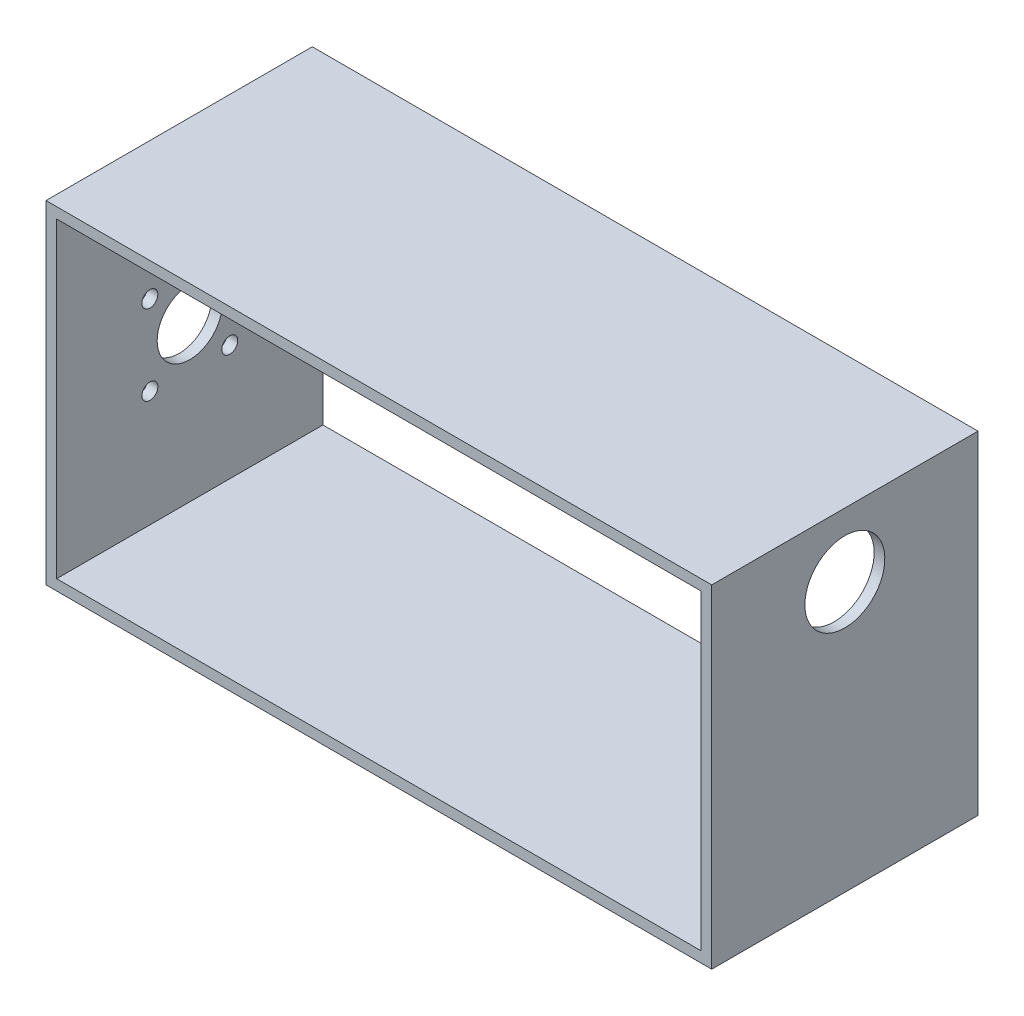
SolidWorks part; units mm, degrees
ref_plane "Ebene vorne" through (0, 0, 0) normal (0, 0, 1) x (1, 0, 0)
ref_plane "Ebene oben" through (0, 0, 0) normal (0, 1, 0) x (1, 0, 0)
ref_plane "Ebene rechts" through (0, 0, 0) normal (1, 0, 0) x (0, 0, -1)
sketch "Skizze1" plane through (0, 0, 0) normal (0, 0, 1) x (1, 0, 0)
  line L1 (0, 125) -> (250, 125)
  line L2 (0, 125) -> (0, 0)
  line L3 (0, 0) -> (250, 0)
  line L4 (250, 125) -> (250, 0)
  line L5 (246, 121) -> (4, 121)
  line L6 (246, 121) -> (246, 4)
  line L7 (246, 4) -> (4, 4)
  line L8 (4, 121) -> (4, 4)
  dimension "D1" = 250
  dimension "D2" = 125
  dimension "D3" = 4
  dimension "D4" = 4
  dimension "D5" = 4
  dimension "D6" = 4
extrude "Aufsatz-Linear austragen1" add sketch "Skizze1" along normal blind 100
sketch "Skizze2" plane through (0, 0, 0) normal (-1, 0, 0) x (0, 0, 1)
  line L0 (0, 125) -> (100, 0) construction
  circle A0 centre (50, 62.5) radius 12.25
extrude "Schnitt-Linear austragen1" cut sketch "Skizze2" against normal blind 10
sketch "Skizze3" plane through (246, 0, 0) normal (-1, 0, 0) x (0, 0, 1)
  line L0 (0, 101) -> (50, 101) construction
  line L1 (0, 4) -> (0, 121) construction
  line L2 (50, 101) -> (100, 101) construction
  line L3 (100, 4) -> (100, 121) construction
  line L4 (50, 101) -> (50, 121) construction
  line L5 (100, 121) -> (0, 121) construction
  circle A0 centre (50, 101) radius 15
extrude "Schnitt-Linear austragen2" cut sketch "Skizze3" against normal blind 10
sketch "Skizze4" plane through (0, 0, 0) normal (-1, 0, 0) x (0, 0, 1)
  line L0 (35, 77.5) -> (65, 77.5) construction
  line L1 (35, 77.5) -> (35, 47.5) construction
  line L2 (35, 47.5) -> (65, 47.5) construction
  line L3 (65, 47.5) -> (65, 77.5) construction
  line L4 (0, 125) -> (0, 0) construction
  line L5 (100, 125) -> (0, 125) construction
  circle A0 centre (35, 77.5) radius 3
  circle A1 centre (65, 77.5) radius 3
  circle A2 centre (65, 47.5) radius 3
  circle A3 centre (35, 47.5) radius 3
  point P2 (73.6, 47.9744)
  point P6 (50, 61.8234)
  point P8 (35.7608, 80.4834)
  point P12 (127.4599, 59.5275)
  point P13 (0, 0)
  point P14 (0, 0)
  dimension "D1" = 35
  dimension "D2" = 47.5
  dimension "D3" = 30
  dimension "D4" = 30
extrude "Schnitt-Linear austragen3" cut sketch "Skizze4" against normal blind 10
